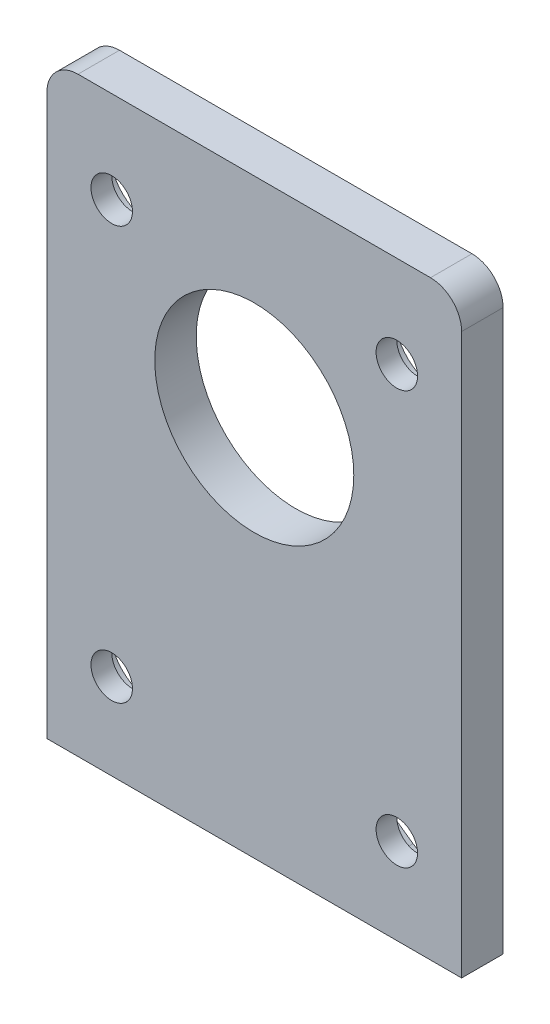
SolidWorks part; units mm, degrees
ref_plane "Front Plane" through (0, 0, 0) normal (0, 0, 1) x (1, 0, 0)
ref_plane "Top Plane" through (0, 0, 0) normal (0, 1, 0) x (1, 0, 0)
ref_plane "Right Plane" through (0, 0, 0) normal (1, 0, 0) x (0, 0, -1)
sketch "Sketch1" plane through (0, 0, 0) normal (0, 0, 1) x (1, 0, 0)
  line L0 (13.75, -19.7) -> (9.6769, -16.8) construction
  line L8 (20, -29) -> (-20, -29)
  line L9 (20, -29) -> (20, 26)
  line L11 (17, 29) -> (-17, 29)
  line L14 (-20, -29) -> (-20, 26)
  line L15 (20, -29) -> (-20, 29) construction
  line L16 (20, 29) -> (-20, -29) construction
  line L17 (11.314, -23.1214) -> (7.2409, -20.2214)
  line L18 (16.186, -16.2786) -> (12.1129, -13.3786)
  line L19 (0, -29) -> (0, 29) construction
  circle A18 centre (-13.75, 20.15) radius 4.2
  circle A19 centre (13.75, 20.15) radius 4.2
  circle A20 centre (-13.75, -19.7) radius 4.2
  arc A21 (11.314, -23.1214) -> (16.186, -16.2786) centre (13.75, -19.7) ccw
  arc A22 (12.1129, -13.3786) -> (7.2409, -20.2214) centre (9.6769, -16.8) ccw
  circle A23 centre (0, 8.8) radius 9.6
  circle A24 centre (-5.725, -6.1) radius 4.2
  circle A25 centre (5.725, -6.1) radius 4.2
  arc A26 (20, 26) -> (17, 29) centre (17, 26) ccw
  arc A27 (-20, 26) -> (-17, 29) centre (-17, 26) cw
  point P0 (0, 0)
  point P9 (4.4053, -19.7)
  point P10 (-17, -19.1957)
  point P12 (0, 0)
  point P13 (0, 0)
  point P14 (6.2555, -14.364)
  point P31 (11.7135, -18.25)
  point P37 (5.725, -10.3)
  point P43 (20, 29)
  point P46 (-20, 29)
  dimension "D1" = 58
  dimension "D2" = 40
  dimension "D3" = 3
  dimension "D4" = 8.4
  dimension "D5" = 8.4
  dimension "D6" = 19.2
  dimension "D7" = 9.3
  dimension "D8" = 27.5
  dimension "D9" = 12.2
  dimension "D10" = 5
  dimension "D11" = 39.85
  dimension "D12" = 20.2
  dimension "D13" = 11.45
  dimension "D14" = 22.9
extrude "Boss-Extrude1" add sketch "Sketch1" along normal blind 2 contours L11 L14 L8 L9 A25 A24 A23 A22 L18 A21 L17 A20 A19 A18 region at (-0.2295, -0.8141, 0)
sketch "Sketch2" plane through (0, -29, 0) normal (0, -1, 0) x (1, 0, 0)
  line L1 (-20, 2) -> (20, 2)
  line L2 (-20, 2) -> (-20, 0)
  line L3 (-20, 0) -> (20, 0)
  line L4 (20, 2) -> (20, 0)
extrude "Cut-Extrude1" cut sketch "Sketch2" against normal blind 1
sketch "Sketch4" plane through (0, 0, 2) normal (0, 0, 1) x (1, 0, 0)
  line L0 (20, -28) -> (20, 26) construction
  line L1 (-17, 29) -> (17, 29)
  line L2 (-20, 26) -> (-20, -28)
  line L3 (-20, -28) -> (20, -28)
  line L4 (20, 26) -> (20, -28)
  line L5 (-20, -28) -> (-20, 26) construction
  line L6 (20, -28) -> (-20, -28) construction
  line L7 (17, 29) -> (-17, 29) construction
  circle A2 centre (-13.75, -19.7) radius 2
  circle A3 centre (-13.75, 20.15) radius 2
  circle A4 centre (13.75, 20.15) radius 2
  arc A8 (17, 29) -> (20, 26) centre (17, 26) cw
  arc A9 (-17, 29) -> (-20, 26) centre (-17, 26) ccw
  circle A10 centre (13.75, -19.7) radius 2
  circle A11 centre (0, 8.8) radius 9.6
  circle A12 centre (0, 8.8) radius 9.6 construction
  dimension "D1" = 4
  dimension "D2" = 3
extrude "Boss-Extrude3" add sketch "Sketch4" along normal blind 2
